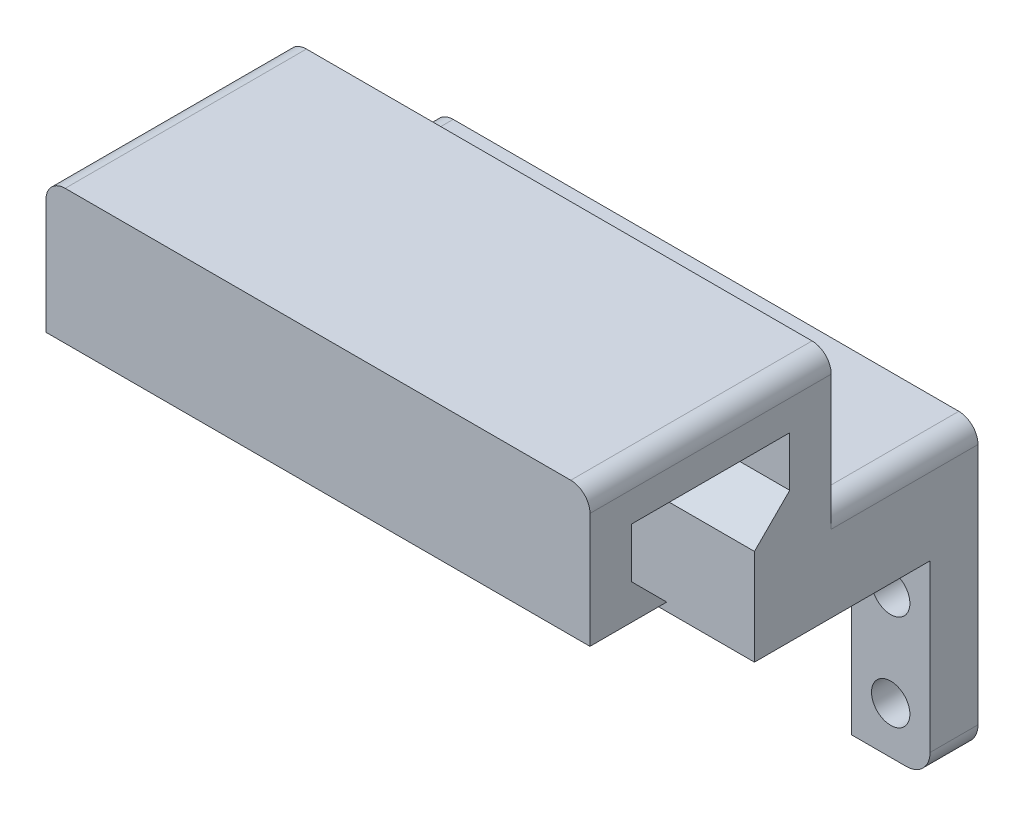
SolidWorks part; units mm, degrees
ref_plane "Alzado" through (0, 0, 0) normal (0, 0, 1) x (1, 0, 0)
ref_plane "Planta" through (0, 0, 0) normal (0, 1, 0) x (1, 0, 0)
ref_plane "Vista lateral" through (0, 0, 0) normal (1, 0, 0) x (0, 0, -1)
sketch "Sketch1" plane through (0, 0, 0) normal (0, 0, 1) x (1, 0, 0)
  line L0 (-24.25, 0) -> (24.25, 0) construction
  line L1 (24.25, -5) -> (24.25, 5) construction
  line L2 (-24.25, -5) -> (-24.25, 5) construction
  line L3 (-24.25, 5) -> (-24.25, 9.9) construction
  line L4 (-24.25, -5) -> (-20.15, -5) construction
  line L5 (-24.25, -5) -> (-24.25, -9.9) construction
  line L6 (-24.25, -5) -> (-28.35, -5) construction
  line L7 (0, -5) -> (0, 5) construction
  line L8 (-20.15, -9.9) -> (-25.85, -9.9)
  line L9 (-20.15, -9.9) -> (-20.15, 9.9)
  line L10 (-20.15, 9.9) -> (-28.35, 9.9)
  line L11 (-28.35, -7.4) -> (-28.35, 9.9)
  line L12 (20.15, 9.9) -> (28.35, 9.9)
  line L13 (28.35, -7.4) -> (28.35, 9.9)
  line L14 (20.15, -9.9) -> (25.85, -9.9)
  line L15 (20.15, -9.9) -> (20.15, 9.9)
  line L17 (-28.35, 9.9) -> (28.35, 9.9)
  line L18 (-28.35, 9.9) -> (-28.35, 17.4)
  line L19 (-25.85, 19.9) -> (25.85, 19.9)
  line L20 (28.35, 9.9) -> (28.35, 17.4)
  circle A0 centre (24.25, -5) radius 2
  circle A1 centre (-24.25, -5) radius 2
  circle A2 centre (-24.25, 5) radius 2
  circle A3 centre (24.25, 5) radius 2
  arc A4 (-28.35, 17.4) -> (-25.85, 19.9) centre (-25.85, 17.4) cw
  arc A5 (25.85, 19.9) -> (28.35, 17.4) centre (25.85, 17.4) cw
  arc A6 (28.35, -7.4) -> (25.85, -9.9) centre (25.85, -7.4) cw
  arc A7 (-25.85, -9.9) -> (-28.35, -7.4) centre (-25.85, -7.4) cw
  point P4 (0, 0)
  point P8 (24.25, 0)
  point P11 (-24.25, 0)
  point P28 (0, 0)
  point P36 (-28.35, 19.9)
  point P41 (28.35, -9.9)
  point P44 (-28.35, -9.9)
  dimension "D2" = 4
  dimension "D6" = 56.7
  dimension "D7" = 48.5
  dimension "D8" = 5
  dimension "D9" = 48.5
  dimension "D10" = 4.9
  dimension "D17" = 4.9
  dimension "D18" = 2.5
  dimension "D1" = 5
  dimension "D3" = 10
  dimension "D4" = 2
  dimension "D11" = 4.1
  dimension "D12" = 4.9
  dimension "D13" = 4.1
  dimension "D14" = 19.8
  dimension "D15" = 8.2
  dimension "D16" = 4.1
  dimension "D5" = 2
extrude "Forma básica" add sketch "Sketch1" along normal blind 5 contours A7 L8 L9 L10 L11 A1 A2 | A6 L13 L12 L15 L14 A3 A0 region at (-24.215, 0.0922, 0) region at (24.215, 0.0922, 0)
extrude "Boss-Extrude2" add sketch "Sketch1<3>" along normal blind 23.3 contours A5 L19 A4 L18 L10 L17 L12 L20 region at (0, 14.8789, 0)
sketch "Sketch1<3>" plane through (0, 0, 0) normal (0, 0, 1) x (1, 0, 0) same geometry as "Sketch1"
sketch "Sketch2" plane through (28.35, 0, 0) normal (1, 0, 0) x (0, 0, -1)
  line L0 (-23.3, 19.9) -> (-19.623, 23.577)
  line L1 (-23.3, 19.9) -> (0, 19.9) construction
  line L2 (-23.3, 19.9) -> (0, 19.9) construction
  line L3 (-19.623, 23.577) -> (-19.623, 28.777)
  line L4 (-19.623, 28.777) -> (-36.123, 28.777)
  line L5 (-36.123, 28.777) -> (-36.123, 23.577)
  line L6 (-36.123, 23.577) -> (-32.4461, 19.9)
  line L7 (-23.3, 19.9) -> (-15.3, 19.9)
  line L8 (-15.3, 19.9) -> (-15.3, 33.9)
  line L9 (-32.4461, 19.9) -> (-40.4461, 19.9)
  line L10 (-40.4461, 19.9) -> (-40.4461, 33.9)
  line L11 (-40.4461, 33.9) -> (-15.3, 33.9)
  dimension "D1" = 5.2
  dimension "D2" = 45
  dimension "D3" = 5.2
  dimension "D4" = 16.5
  dimension "D5" = 5.2
  dimension "D6" = 45
  dimension "D7" = 9.1461
  dimension "D8" = 8
  dimension "D9" = 14
  dimension "D10" = 8
extrude "Carril cremallera" add sketch "Sketch2" against normal up to surface (56.7 mm away) up to face at (-28.35, 6.6333, 9.4333)
sketch "Sketch3" plane through (0, 0, 23.3) normal (0, 0, 1) x (1, 0, 0)
  line L0 (-28.35, 17.4) -> (-28.35, 19.9)
  line L1 (-28.35, 19.9) -> (28.35, 19.9) construction
  line L2 (-28.35, 19.9) -> (-25.85, 19.9)
  line L3 (0, 0) -> (0, 33.9) construction
  line L4 (-28.35, 33.9) -> (28.35, 33.9) construction
  line L5 (28.35, 19.9) -> (25.85, 19.9)
  line L6 (28.35, 17.4) -> (28.35, 19.9)
  arc A0 (-25.85, 19.9) -> (-28.35, 17.4) centre (-25.85, 17.4) ccw
  arc A1 (25.85, 19.9) -> (28.35, 17.4) centre (25.85, 17.4) cw
extrude "Eliminar filete" add sketch "Sketch3" against normal up to surface (23.3 mm away) up to face at (0, 3.3333, 0)
fillet "Fillet2" radius 2 4 edges at (-28.35, 19.9, 7.65) (28.35, 19.9, 7.65) (28.35, 33.9, 27.873) (-28.35, 33.9, 27.873)
